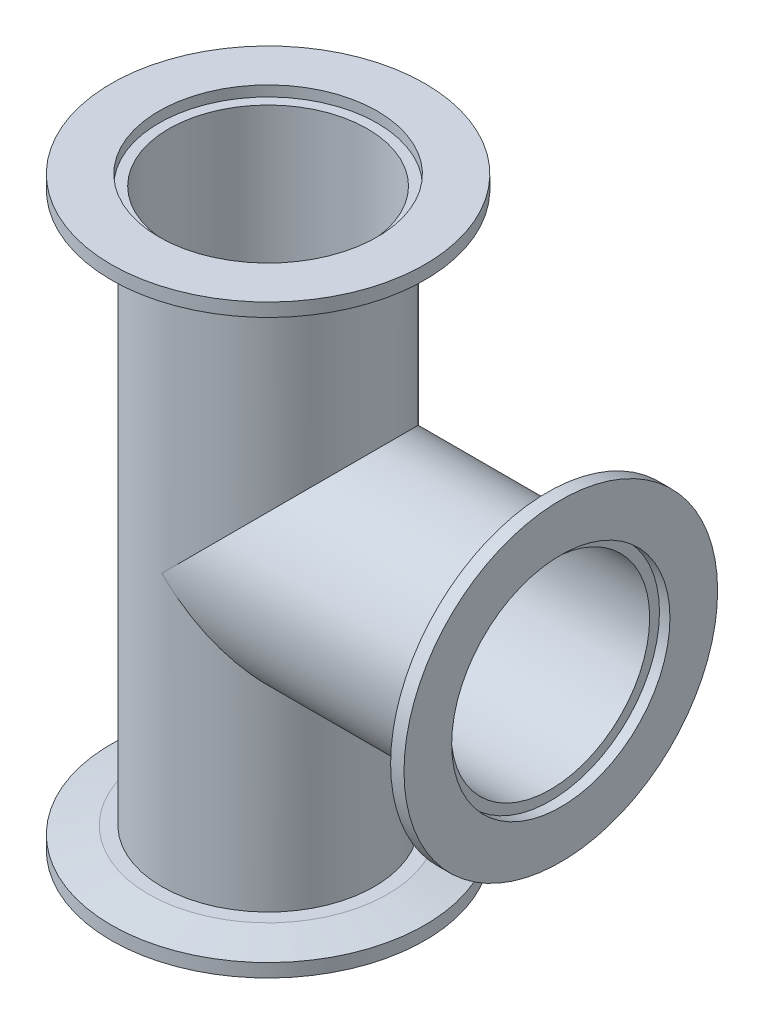
SolidWorks part; units mm, degrees
material "AISI 316 Annealed Stainless Steel Bar (SS)"
ref_plane "Front Plane" through (0, 0, 0) normal (0, 0, 1) x (1, 0, 0)
ref_plane "Top Plane" through (0, 0, 0) normal (0, 1, 0) x (1, 0, 0)
ref_plane "Right Plane" through (0, 0, 0) normal (1, 0, 0) x (0, 0, -1)
sketch "Sketch1" plane through (0, 0, 0) normal (1, 0, 0) x (0, 0, -1)
  line L0 (0, 0) -> (0, -64.9) construction
  line L1 (-37.5, -70) -> (-37.5, -66.8)
  line L2 (-37.5, -66.8) -> (-28.5612, -64.9)
  line L3 (0, 0) -> (24.3767, 0) construction
  line L6 (0, -67.5) -> (-26.1, -67.5)
  line L7 (-26.1, -67.5) -> (-26.1, -70)
  line L8 (-26.1, -70) -> (-37.5, -70)
  line L9 (-28.5612, -64.9) -> (0, -64.9)
  line L10 (0, -64.9) -> (0, -67.5)
  dimension "D1" = 78
  dimension "D2" = 57.1224
  dimension "Flange ID" = 52.2
  dimension "D3" = 140
  dimension "Flange OD" = 75
  dimension "D5" = 3.2
  dimension "Flange Height" = 5.1
  dimension "D9" = 2.5
revolve "Flange" add sketch "Sketch1" angle 360 about L0
sketch "Sketch5" plane through (0, -67.5, 0) normal (0, -1, 0) x (1, 0, 0)
  circle A0 centre (0, 0) radius 25.4
  dimension "Outer Diameter" = 50.8
extrude "Stub" add sketch "Sketch5" against normal up to surface (67.5 mm away) up to plane "Top Plane"
ref_plane "Plane1" through (0, -71.905, 0) normal (0, -1, 0) x (-1, 0, 0)
ref_axis "Axis1" through (-32.125, 0, 0) along (1, 0, 0)
ref_axis "Axis2" through (0, 0, -30.25) along (0, 0, 1)
pattern_circular "CirPattern1" count 3 every 90 about axis through (0, 0, -30.25) along (0, 0, 1) of bodies 120
combine bodies "Combine1" operation type add bodies to combine 120 139 140
sketch "Bore Sketch" plane through (0, 0, 0) normal (0, 1, 0) x (1, 0, 0)
  circle A0 centre (0, 0) radius 23.75
  dimension "d1" = 47.5
extrude "Bore" cut sketch "Bore Sketch" against normal through all
pattern_circular "CirPattern2" count 3 every 90 about axis through (0, 0, -30.25) along (0, 0, 1) of "Bore"
ref_plane "Plane2" through (71.905, 0, 0) normal (1, 0, 0) x (0, 0, -1)
ref_plane "Plane3" through (0, 71.905, 0) normal (0, 1, 0) x (1, 0, 0)
equation "\"D1@Plane3\"= \"D1@Plane1\""
